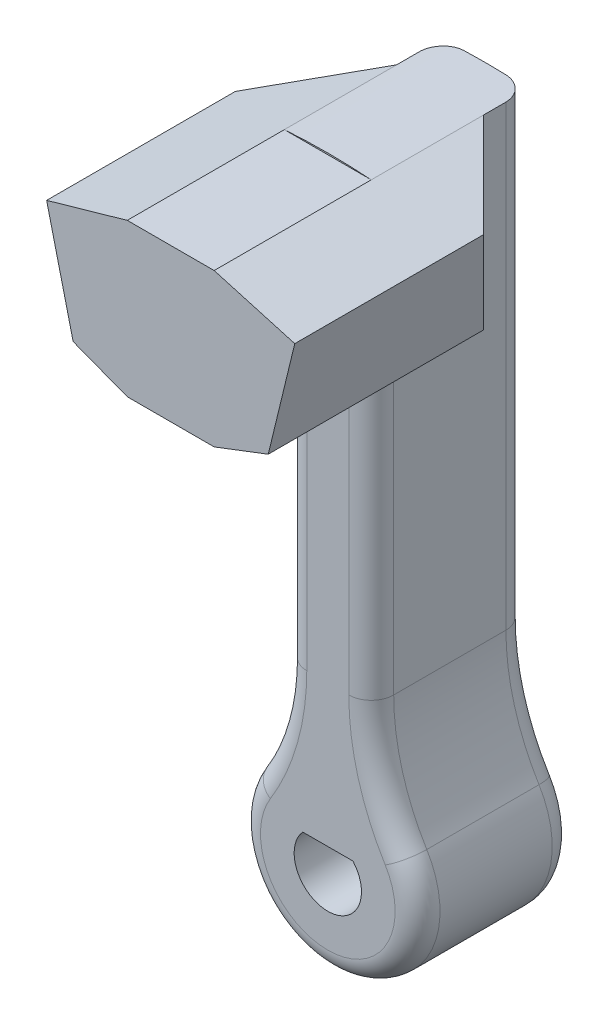
SolidWorks part; units mm, degrees
ref_plane "Alzado" through (0, 0, 0) normal (0, 0, 1) x (1, 0, 0)
ref_plane "Planta" through (0, 0, 0) normal (0, 1, 0) x (1, 0, 0)
ref_plane "Vista lateral" through (0, 0, 0) normal (1, 0, 0) x (0, 0, -1)
sketch "Croquis1" plane through (0, 0, 21.25) normal (0, 0, 1) x (1, 0, 0)
  line L1 (-25.3164, -1.5169) -> (-29.1894, -1.5169)
  line L2 (-26.1348, -4.0169) -> (-28.3709, -4.0169)
  line L3 (-26.1348, -4.0169) -> (-28.3709, -4.0169)
  arc A1 (-29.1894, -1.5169) -> (-25.3164, -1.5169) centre (-27.2529, -5.0169) ccw
  arc A2 (-28.3709, -4.0169) -> (-26.1348, -4.0169) centre (-27.2529, -5.0169) ccw
  arc A3 (-28.3709, -4.0169) -> (-26.1348, -4.0169) centre (-27.2529, -5.0169) ccw
  dimension "D1" = 0
  dimension "D2" = 2.5
extrude "Saliente-Extruir1" add sketch "Croquis1" against normal blind 7
sketch "Croquis2" plane through (0, 0, 14.25) normal (0, 0, -1) x (-1, 0, 0)
  line L0 (25.3164, -1.5169) -> (25.3164, 22.6766)
  line L1 (29.1894, -1.5169) -> (29.1894, 22.6766)
  line L2 (25.3164, -1.5169) -> (29.1894, -1.5169)
  arc A2 (29.1894, 22.6766) -> (25.3164, 22.6766) centre (27.2529, -5.0169) ccw
extrude "Saliente-Extruir2" add sketch "Croquis2" against normal blind 7
sketch "Croquis3" plane through (0, 0, 21.25) normal (0, 0, -1) x (-1, 0, 0)
  line L0 (27.2529, 22.7442) -> (27.2529, 9.9898) construction
  line L1 (25.3164, 22.6766) -> (21.7248, 21.6519)
  line L2 (21.7248, 21.6519) -> (22.9059, 16.7934)
  line L3 (22.9059, 16.7934) -> (25.3164, 15.87)
  line L4 (25.3164, 22.6766) -> (25.3164, -1.5169) construction
  line L6 (31.5999, 16.7934) -> (29.1894, 15.87)
  line L7 (32.7809, 21.6519) -> (31.5999, 16.7934)
  line L8 (29.1894, 22.6766) -> (32.7809, 21.6519)
  line L10 (25.3164, 22.6766) -> (29.1894, 22.6766)
  line L11 (25.3164, 15.87) -> (29.1894, 15.87)
  arc A0 (29.1894, 22.6766) -> (25.3164, 22.6766) centre (27.2529, -5.0169) ccw construction
extrude "Saliente-Extruir3" add sketch "Croquis3" against normal blind 7
fillet "Redondeo1" radius 10 2 edges at (-29.1894, -1.5169, 17.75) (-25.3164, -1.5169, 17.75)
fillet "Redondeo2" radius 1 5 edges at (-29.1894, 12.4877, 14.25) (-29.5649, -0.4159, 14.25) (-25.3164, 12.4877, 14.25) (-24.9409, -0.4159, 14.25) (-27.2529, -9.0169, 14.25)
fillet "Redondeo3" radius 1 5 edges at (-25.3164, 9.0844, 21.25) (-24.9409, -0.4159, 21.25) (-27.2529, -9.0169, 21.25) (-29.5649, -0.4159, 21.25) (-29.1894, 9.0844, 21.25)
chamfer "Chaflán1" distance 5 angle 45 2 edges at (-25.3164, 19.2733, 21.25) (-29.1894, 19.2733, 21.25)
